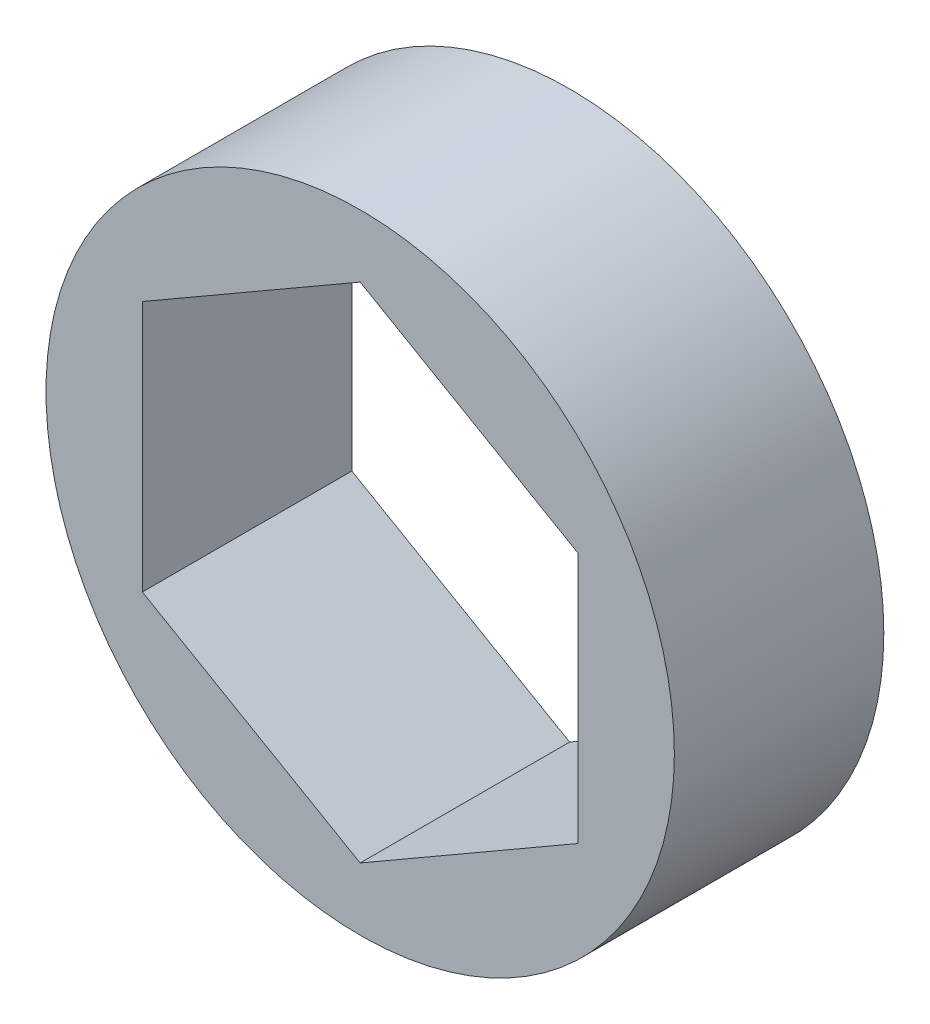
SolidWorks part; units mm, degrees
material "PET"
ref_plane "Front Plane" through (0, 0, 0) normal (0, 0, 1) x (1, 0, 0)
ref_plane "Top Plane" through (0, 0, 0) normal (0, 1, 0) x (1, 0, 0)
ref_plane "Right Plane" through (0, 0, 0) normal (1, 0, 0) x (0, 0, -1)
sketch "Sketch1" plane through (0, 0, 0) normal (0, 0, 1) x (1, 0, 0)
  line L1 (0, 7.6256) -> (-6.604, 3.8128)
  line L2 (-6.604, 3.8128) -> (-6.604, -3.8128)
  line L3 (-6.604, -3.8128) -> (0, -7.6256)
  line L4 (0, -7.6256) -> (6.604, -3.8128)
  line L5 (6.604, -3.8128) -> (6.604, 3.8128)
  line L6 (6.604, 3.8128) -> (0, 7.6256)
  circle A0 centre (0, 0) radius 6.604 construction
  circle A1 centre (0, 0) radius 9.525
  dimension "D1" = 13.208
  dimension "D2" = 19.05
extrude "Boss-Extrude1" add sketch "Sketch1" along normal mid plane 6.35
